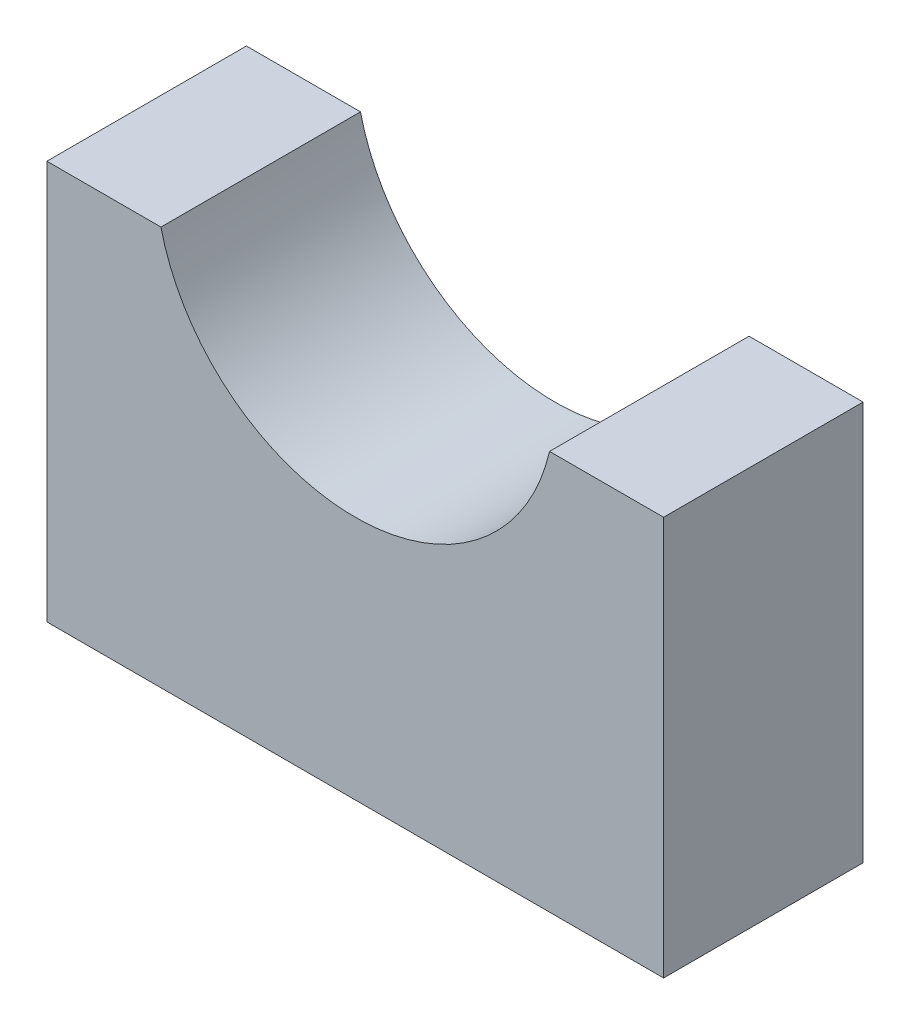
SolidWorks part; units mm, degrees
ref_plane "Front Plane" through (0, 0, 0) normal (0, 0, 1) x (1, 0, 0)
ref_plane "Top Plane" through (0, 0, 0) normal (0, 1, 0) x (1, 0, 0)
ref_plane "Right Plane" through (0, 0, 0) normal (1, 0, 0) x (0, 0, -1)
sketch "Sketch1" plane through (0, 0, 0) normal (0, 0, 1) x (1, 0, 0)
  line L0 (-17, 0) -> (17, 0) construction
  line L1 (0, 0) -> (0, -11) construction
  line L2 (-17, -2.5) -> (17, -2.5)
  line L4 (-17, -2.5) -> (-17, -24.5)
  line L5 (-17, -24.5) -> (17, -24.5)
  line L6 (17, -24.5) -> (17, -2.5)
  circle A0 centre (0, 0) radius 11
  dimension "D1" = 22
  dimension "D2" = 17
  dimension "D5" = 22
  dimension "D3" = 2.5
extrude "Boss-Extrude1" add sketch "Sketch1" along normal blind 11 contours A0 L2 L4 L5 L6 region at (0, -15.1497, 0)
